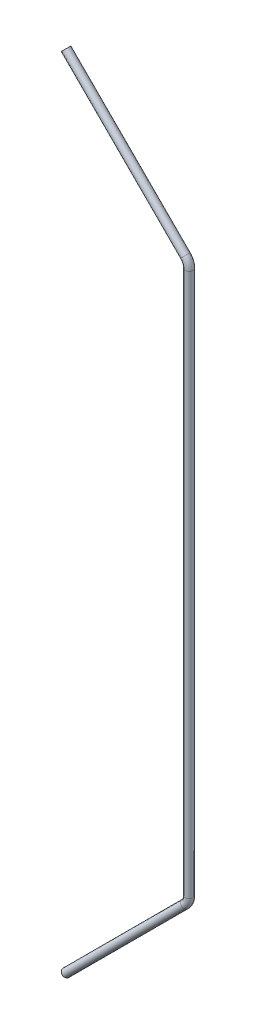
SolidWorks part; units mm, degrees
ref_plane "Plano frontal" through (0, 0, 0) normal (0, 0, 1) x (1, 0, 0)
ref_plane "Plano superior" through (0, 0, 0) normal (0, 1, 0) x (1, 0, 0)
ref_plane "Plano direito" through (0, 0, 0) normal (1, 0, 0) x (0, 0, -1)
sketch3d "3DSketch2"
  line L0 (-23026.9468, -1831.2729, 40306.6002) -> (-23026.9468, 11668.7271, 40306.6002) construction
  line L1 (-23026.9468, 11555.5219, 40306.6002) -> (-23026.9468, -1831.2729, 40306.6002) construction
  line L2 (-23026.9468, 6719.906, 40306.6002) -> (-22077.4463, 6719.906, 40306.6002) construction
  line L3 (-22077.4463, 6719.906, 40306.6002) -> (-22077.4463, 2448.4194, 40306.6002) construction
  line L4 (-22077.4463, 2448.4194, 40306.6002) -> (-23026.9468, 2448.4194, 40306.6002) construction
  line L5 (-23026.9468, 7669.4065, 40306.6002) -> (-22106.7357, 6749.1954, 40306.6002)
  line L6 (-22077.4463, 6678.4847, 40306.6002) -> (-22077.4463, 2489.8408, 40306.6002)
  line L7 (-22106.7357, 2419.1301, 40306.6002) -> (-23026.9468, 1498.919, 40306.6002)
  arc A0 (-22106.7357, 6749.1954, 40306.6002) -> (-22077.4463, 6678.4847, 40306.6002) centre (-22177.4463, 6678.4847, 40306.6002) ccw
  arc A1 (-22077.4463, 2489.8408, 40306.6002) -> (-22106.7357, 2419.1301, 40306.6002) centre (-22177.4463, 2489.8408, 40306.6002) ccw
  point P9 (-23026.9468, 1662.4232, 40306.6002)
  point P12 (-22077.4463, 6719.906, 40306.6002)
  point P15 (-22177.4463, 6678.4847, 40206.6002)
  point P18 (-22077.4463, 2448.4194, 40306.6002)
  point P20 (-22177.4463, 2489.8408, 40206.6002)
  dimension "D3" = 100
  dimension "D1" = 45
  dimension "D2" = 45
sweep "Sweep-Thin1" add path "3DSketch2" circular profile diameter 60 parameters "D1"=3, "D3"=60
